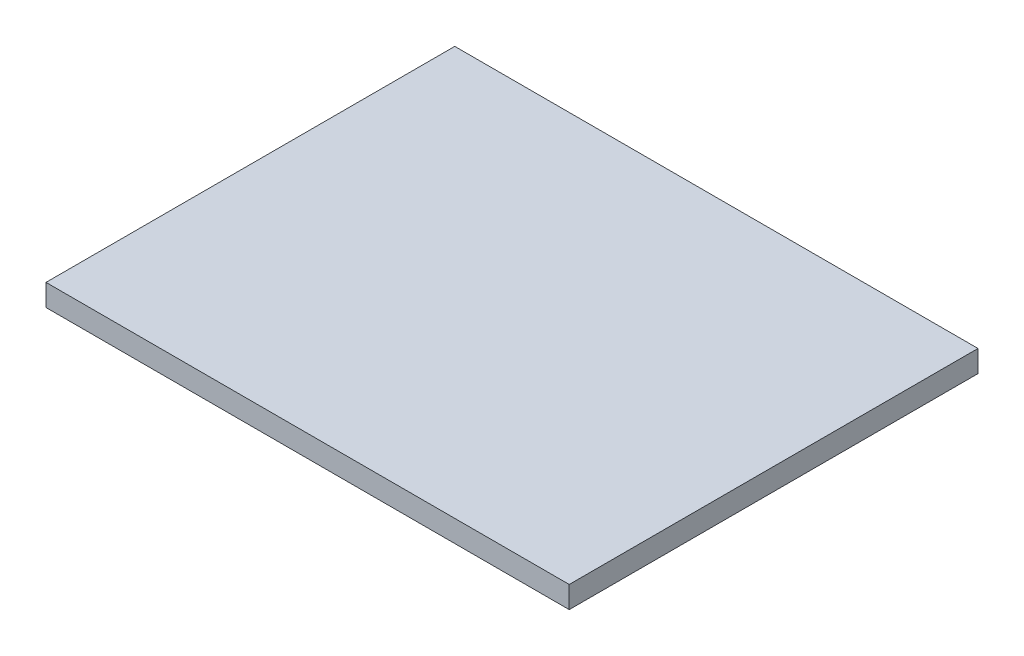
SolidWorks part; units mm, degrees
ref_plane "Front Plane" through (0, 0, 0) normal (0, 0, 1) x (1, 0, 0)
ref_plane "Top Plane" through (0, 0, 0) normal (0, 1, 0) x (1, 0, 0)
ref_plane "Right Plane" through (0, 0, 0) normal (1, 0, 0) x (0, 0, -1)
ref_plane "Plane1" through (0, -8, 0) normal (0, -1, 0) x (-1, 0, 0)
sketch "Sketch1" plane through (0, -8, 0) normal (0, -1, 0) x (-1, 0, 0)
  line L0 (-2, 75) -> (-2, 0) construction
  line L1 (-2, 0) -> (-98, 0)
  line L2 (-2, 0) -> (-2, 75)
  line L3 (-2, 75) -> (-98, 75)
  line L4 (-98, 0) -> (-98, 75)
  line L5 (2, 75) -> (-2, 75) construction
extrude "Boss-Extrude1" add sketch "Sketch1" against normal blind 4
